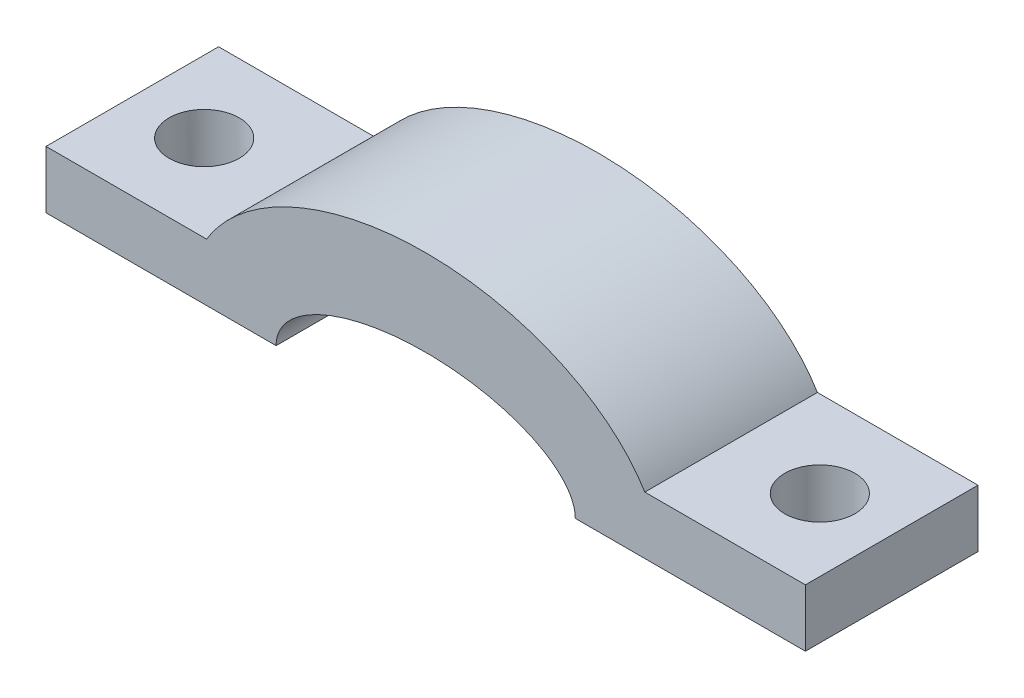
SolidWorks part; units mm, degrees
ref_plane "Front Plane" through (0, 0, 0) normal (0, 0, 1) x (1, 0, 0)
ref_plane "Top Plane" through (0, 0, 0) normal (0, 1, 0) x (1, 0, 0)
ref_plane "Right Plane" through (0, 0, 0) normal (1, 0, 0) x (0, 0, -1)
sketch "Sketch2" plane through (0, 0, 0) normal (0, 0, 1) x (1, 0, 0)
  line L0 (-20.5, 0) -> (20.5, 0)
  ellipse E0 centre (0, 0) end of major axis (13, 0) minor radius 6
  ellipse E1 centre (0, 0) end of major axis (20.5, 0) minor radius 13.5
  dimension "D1" = 26
  dimension "D2" = 12
  dimension "D3" = 41
  dimension "D4" = 27
extrude "Boss-Extrude1" add sketch "Sketch2" along normal blind 15 contours L0 E1 E0 region at (0, 6.9788, 0)
sketch "Sketch3" plane through (0, 0, 0) normal (0, -1, 0) x (1, 0, 0)
  line L1 (13, 15) -> (33, 15)
  line L2 (13, 15) -> (13, 0)
  line L3 (13, 0) -> (33, 0)
  line L4 (33, 15) -> (33, 0)
  line L5 (-13, 15) -> (-33, 15)
  line L6 (-13, 15) -> (-13, 0)
  line L7 (-13, 0) -> (-33, 0)
  line L8 (-33, 15) -> (-33, 0)
  dimension "D1" = 20
extrude "Boss-Extrude2" add sketch "Sketch3" against normal blind 5
sketch "Sketch5" plane through (0, 5, 0) normal (0, 1, 0) x (1, 0, 0)
  line L0 (19.0421, 0) -> (19.0421, -15) construction
  line L1 (19.0421, 0) -> (33, 0) construction
  line L2 (0, 0) -> (0, -15) construction
  line L3 (-19.0421, -15) -> (19.0421, -15) construction
  circle A0 centre (26.7521, -7.5) radius 3.05
  circle A1 centre (-26.7521, -7.5) radius 3.05
  dimension "D1" = 6.1
  dimension "D3" = 7.5
  dimension "D2" = 7.71
extrude "Cut-Extrude2" cut sketch "Sketch5" against normal blind 10
